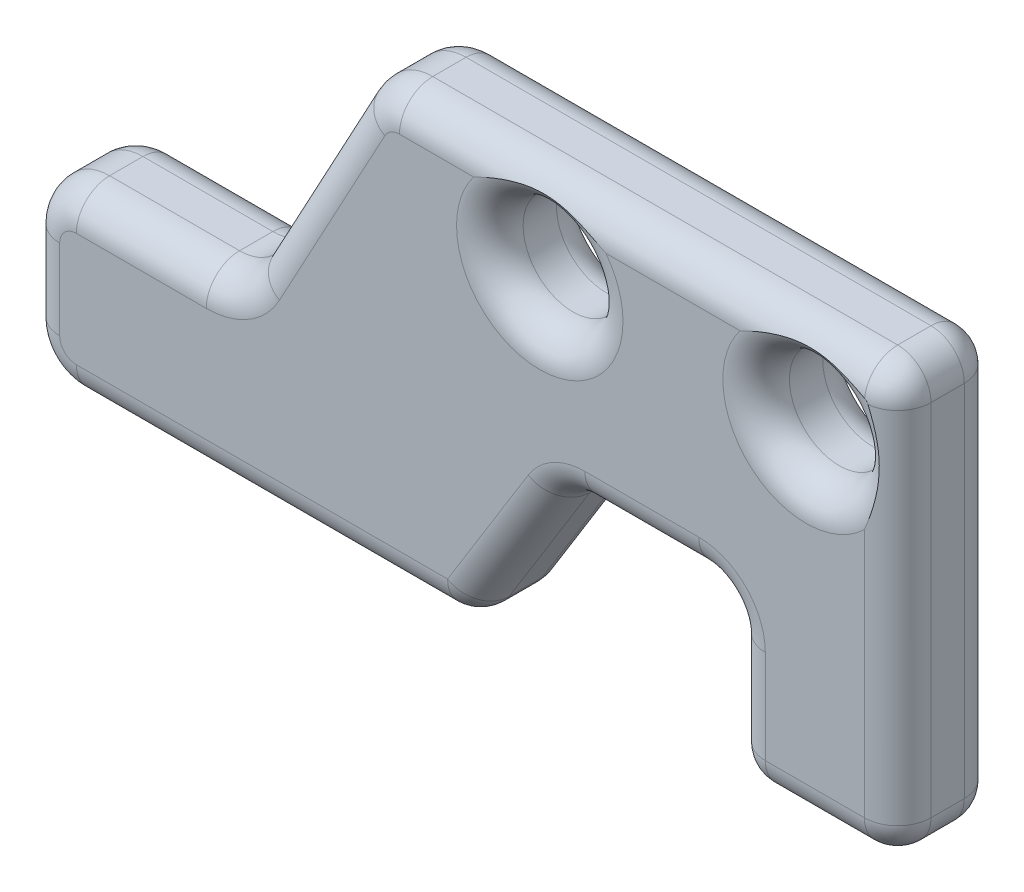
SolidWorks part; units mm, degrees
ref_plane "Front Plane" through (0, 0, 0) normal (0, 0, 1) x (1, 0, 0)
ref_plane "Top Plane" through (0, 0, 0) normal (0, 1, 0) x (1, 0, 0)
ref_plane "Right Plane" through (0, 0, 0) normal (1, 0, 0) x (0, 0, -1)
sketch "Sketch1" plane through (0, 0, 0) normal (0, 0, 1) x (1, 0, 0)
  line L0 (15.8342, -6.2247) -> (30.8017, -6.2247)
  line L1 (30.8017, -6.2247) -> (30.8017, -19.0273)
  line L2 (30.8017, -19.0273) -> (25.8249, -19.0273)
  line L3 (25.8249, -19.0273) -> (25.8249, -14.2122)
  line L4 (25.8249, -14.2122) -> (20.848, -14.2122)
  line L5 (20.848, -14.2122) -> (17.8376, -19.0752)
  line L6 (17.8376, -19.0752) -> (6.1271, -19.0752)
  line L7 (4.6271, -17.5752) -> (4.6271, -15.1592)
  line L8 (6.1271, -13.6592) -> (10.0298, -13.6592)
  line L9 (11.3496, -12.872) -> (14.5144, -7.0119)
  circle A0 centre (20.0493, -8.7438) radius 1.5
  circle A1 centre (28.0493, -8.7438) radius 1.5
  arc A2 (10.0298, -13.6592) -> (11.3496, -12.872) centre (10.0298, -12.1592) ccw
  arc A3 (15.8342, -6.2247) -> (14.5144, -7.0119) centre (15.8342, -7.7247) ccw
  arc A4 (6.1271, -19.0752) -> (4.6271, -17.5752) centre (6.1271, -17.5752) cw
  arc A5 (4.6271, -15.1592) -> (6.1271, -13.6592) centre (6.1271, -15.1592) cw
  point P4 (14.458, -12.5533)
  point P15 (20.848, -14.2122)
  dimension "D1" = 3
  dimension "D2" = 3
  dimension "D4" = 1.5
  dimension "D3" = 8
extrude "Boss-Extrude1" add sketch "Sketch1" along normal blind 3
fillet "Fillet1" radius 1 38 edges at (30.8017, -12.626, 3) (30.8017, -12.626, 0) (30.8017, -6.2247, 1.5) (23.318, -6.2247, 3) (23.318, -6.2247, 0) (15.0658, -6.4364, 3) (15.0658, -6.4364, 0) (12.932, -9.942, 3) (12.932, -9.942, 0) (10.7982, -13.4475, 3) (10.7982, -13.4475, 0) (8.0785, -13.6592, 3) (8.0785, -13.6592, 0) (5.0665, -14.0986, 3) (5.0665, -14.0986, 0) (4.6271, -16.3672, 3) (4.6271, -16.3672, 0) (5.0665, -18.6358, 3) (5.0665, -18.6358, 0) (11.9824, -19.0752, 3) (11.9824, -19.0752, 0) (17.8376, -19.0752, 1.5) (19.3428, -16.6437, 3) (19.3428, -16.6437, 0) (20.848, -14.2122, 1.5) (23.3365, -14.2122, 3) (23.3365, -14.2122, 0) (25.8249, -14.2122, 1.5) (25.8249, -16.6198, 3) (25.8249, -16.6198, 0) (25.8249, -19.0273, 1.5) (28.3133, -19.0273, 3) (30.8017, -19.0273, 1.5) (28.3133, -19.0273, 0) (21.5493, -8.7438, 0) (21.5493, -8.7438, 3) (29.5493, -8.7438, 0) (29.5493, -8.7438, 3)
